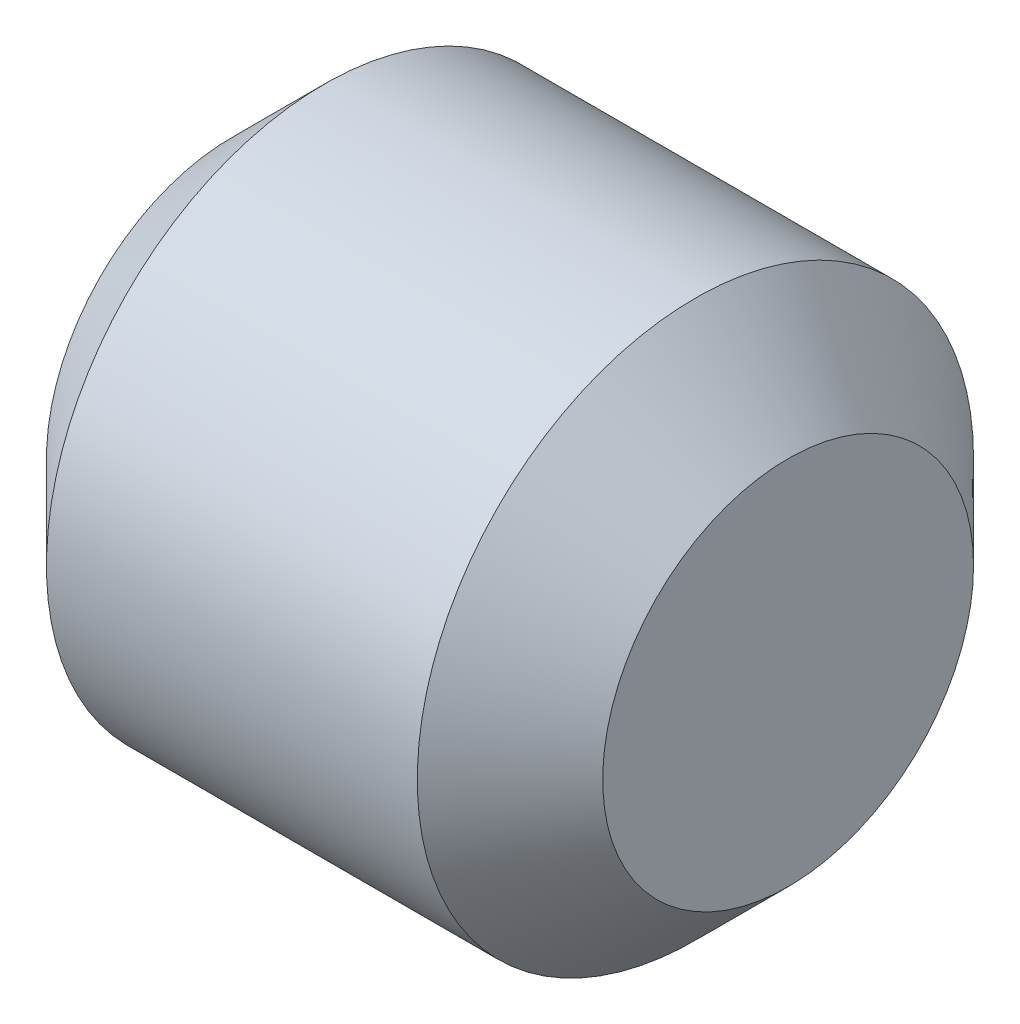
SolidWorks part; units mm, degrees
ref_plane "Front" through (0, 0, 0) normal (0, 0, 1) x (1, 0, 0)
ref_plane "Top" through (0, 0, 0) normal (0, 1, 0) x (1, 0, 0)
ref_plane "Right" through (0, 0, 0) normal (1, 0, 0) x (0, 0, -1)
sketch "Sketch1" plane through (0, 0, 0) normal (1, 0, 0) x (0, 0, -1)
  circle A0 centre (0, 0) radius 300
extrude "Boss-Extrude1" add sketch "Sketch1" along normal blind 400
extrude "Boss-Extrude2" add sketch "Sketch1<2>" against normal blind 100 draft 45
sketch "Sketch1<2>" plane through (0, 0, 0) normal (1, 0, 0) x (0, 0, -1) same geometry as "Sketch1"
extrude "Boss-Extrude3" add sketch "Sketch1<3>" along normal blind 100 draft 45 from offset 400
sketch "Sketch1<3>" plane through (0, 0, 0) normal (1, 0, 0) x (0, 0, -1) same geometry as "Sketch1"
